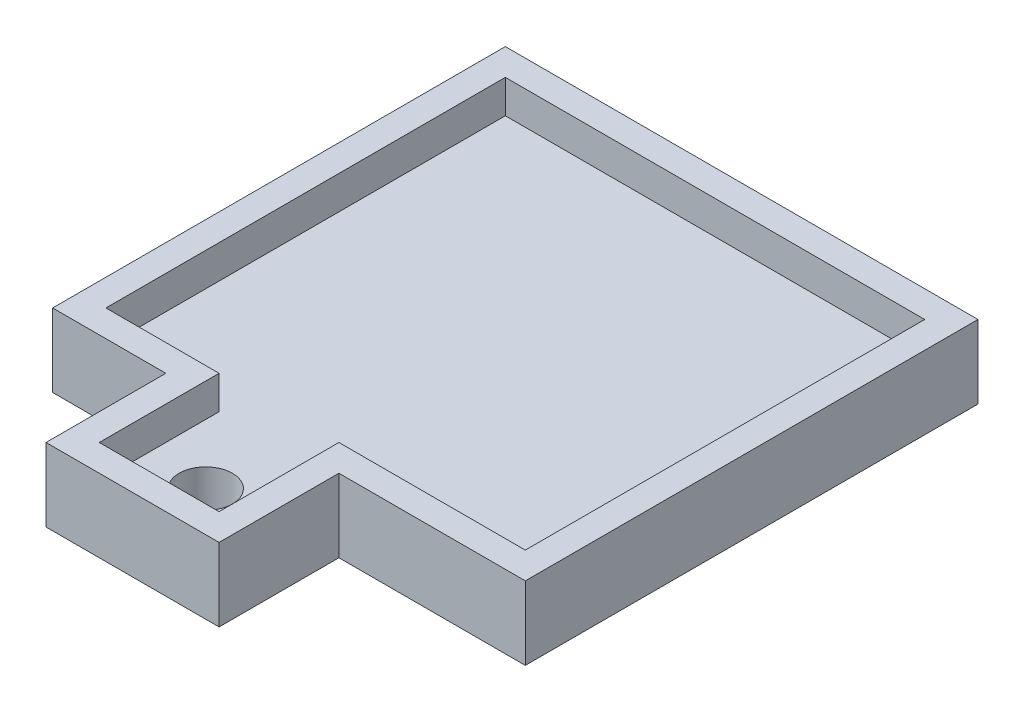
SolidWorks part; units mm, degrees
ref_plane "Front Plane" through (0, 0, 0) normal (0, 0, 1) x (1, 0, 0)
ref_plane "Top Plane" through (0, 0, 0) normal (0, 1, 0) x (1, 0, 0)
ref_plane "Right Plane" through (0, 0, 0) normal (1, 0, 0) x (0, 0, -1)
sketch "Sketch1" plane through (0, 0, 0) normal (0, 1, 0) x (1, 0, 0)
  line L1 (-157.5, 300) -> (157.5, 300)
  line L2 (-157.5, 300) -> (-157.5, 0)
  line L3 (157.5, 300) -> (157.5, 0)
  line L4 (-157.5, 0) -> (-72.5, 0)
  line L5 (-157.5, 0) -> (-72.5, 0)
  line L6 (-72.5, 0) -> (-72.5, -90)
  line L7 (-72.5, -90) -> (17.5, -90)
  line L8 (17.5, -90) -> (17.5, 0)
  line L9 (17.5, 0) -> (157.5, 0)
  circle A0 centre (-27.5, -55) radius 20
extrude "Boss-Extrude1" add sketch "Sketch1" along normal blind 30 contours L8 L9 L3 L1 L2 L4 L6 L7 A0 region at (-1.857, 0, -136.9563)
scale "Scale1" scale about centroid uniform scaling yes scale factor 0.1
sketch "Sketch2" plane through (0, 13.5, 0) normal (0, -1, 0) x (1, 0, 0)
  line L0 (-19.4213, -155.2607) -> (-19.4213, -121.2607)
  line L2 (14.0787, -153.2607) -> (14.0787, -123.2607)
  line L3 (16.0787, -155.2607) -> (-19.4213, -155.2607)
  line L5 (2.0787, -112.2607) -> (-10.9213, -112.2607)
  line L7 (16.0787, -155.2607) -> (16.0787, -121.2607)
  line L9 (16.0787, -121.2607) -> (2.0787, -121.2607)
  line L10 (-10.9213, -121.2607) -> (-19.4213, -121.2607)
  line L11 (2.0787, -121.2607) -> (2.0787, -112.2607)
  line L13 (-10.9213, -112.2607) -> (-10.9213, -121.2607)
  line L16 (14.0787, -123.2607) -> (0.0787, -123.2607)
  line L18 (0.0787, -123.2607) -> (0.0787, -114.2607)
  line L19 (0.0787, -114.2607) -> (-8.9213, -114.2607)
  line L20 (-8.9213, -114.2607) -> (-8.9213, -123.2607)
  line L21 (-8.9213, -123.2607) -> (-17.4213, -123.2607)
  line L22 (-17.4213, -123.2607) -> (-17.4213, -153.2607)
  line L23 (-17.4213, -153.2607) -> (14.0787, -153.2607)
extrude "Boss-Extrude2" add sketch "Sketch2" against normal blind 5.5
